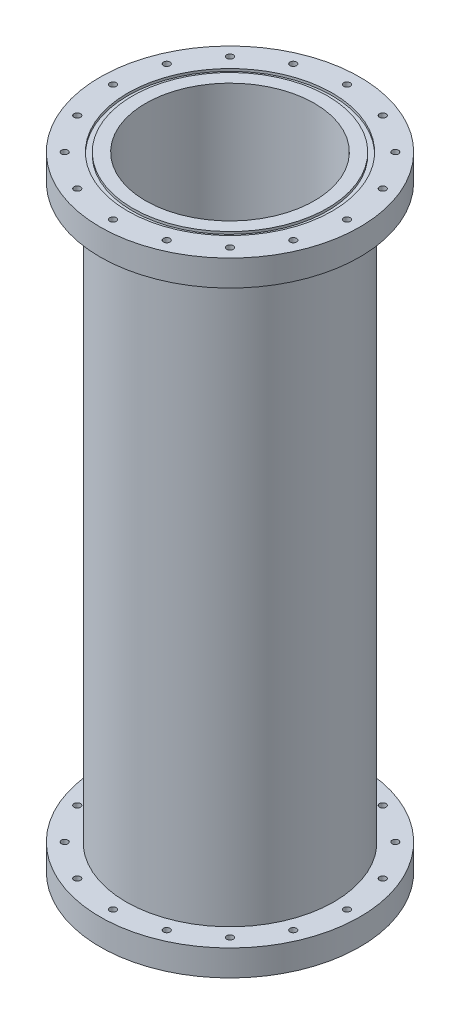
SolidWorks part; units mm, degrees
ref_plane "Front Plane" through (0, 0, 0) normal (0, 0, 1) x (1, 0, 0)
ref_plane "Top Plane" through (0, 0, 0) normal (0, 1, 0) x (1, 0, 0)
ref_plane "Right Plane" through (0, 0, 0) normal (1, 0, 0) x (0, 0, -1)
sketch "Sketch2" plane through (0, 0, 0) normal (0, 1, 0) x (1, 0, 0)
  circle A0 centre (0, 0) radius 41.275
  circle A1 centre (0, 0) radius 50.8
  dimension "D1" = 101.6
  dimension "D2" = 82.55
extrude "Base Cylinder" add sketch "Sketch2" along normal blind 304.8
sketch "Sketch3" plane through (0, 0, 0) normal (0, -1, 0) x (1, 0, 0)
  circle A0 centre (0, 0) radius 41.275
  circle A1 centre (0, 0) radius 63.5
  dimension "D1" = 127
extrude "Aft Flange" add sketch "Sketch3" against normal blind 12.7
sketch "Sketch4" plane through (0, 304.8, 0) normal (0, 1, 0) x (1, 0, 0)
  circle A0 centre (0, 0) radius 41.275
  circle A1 centre (0, 0) radius 63.5
extrude "Forward Flange" add sketch "Sketch4" against normal blind 12.7
sketch "Sketch6" plane through (0, 0, 0) normal (0, -1, 0) x (1, 0, 0)
  circle A0 centre (0, 0) radius 50.0062
  circle A1 centre (0, 0) radius 47.625
  dimension "D1" = 100.0125
  dimension "D2" = 95.25
extrude "O-Ring Slot 1" cut sketch "Sketch6" against normal blind 1.1906
sketch "Sketch7" plane through (0, 304.8, 0) normal (0, 1, 0) x (1, 0, 0)
  circle A0 centre (0, 0) radius 50.0062
  circle A1 centre (0, 0) radius 47.625
  dimension "D1" = 100.0125
  dimension "D2" = 95.25
extrude "O-Ring Slot 2" cut sketch "Sketch7" against normal blind 1.1906
sketch "Sketch8" plane through (0, 0, 0) normal (0, -1, 0) x (1, 0, 0)
  circle A0 centre (-57.15, 0) radius 1.5875
  circle A1 centre (-52.7997, 21.8704) radius 1.5875
  circle A2 centre (-40.4112, 40.4112) radius 1.5875
  circle A3 centre (-21.8704, 52.7997) radius 1.5875
  circle A4 centre (0, 57.15) radius 1.5875
  circle A5 centre (21.8704, 52.7997) radius 1.5875
  circle A6 centre (40.4112, 40.4112) radius 1.5875
  circle A7 centre (52.7997, 21.8704) radius 1.5875
  circle A8 centre (57.15, 0) radius 1.5875
  circle A9 centre (52.7997, -21.8704) radius 1.5875
  circle A10 centre (40.4112, -40.4112) radius 1.5875
  circle A11 centre (21.8704, -52.7997) radius 1.5875
  circle A12 centre (0, -57.15) radius 1.5875
  circle A13 centre (-21.8704, -52.7997) radius 1.5875
  circle A14 centre (-40.4112, -40.4112) radius 1.5875
  circle A15 centre (-52.7997, -21.8704) radius 1.5875
  point P36 (0, 0)
  dimension "D2" = 3.175
  dimension "D1" = 57.15
  dimension "D3" = 16
extrude "Cut-Extrude4" cut sketch "Sketch8" against normal through all both and the other way through all
